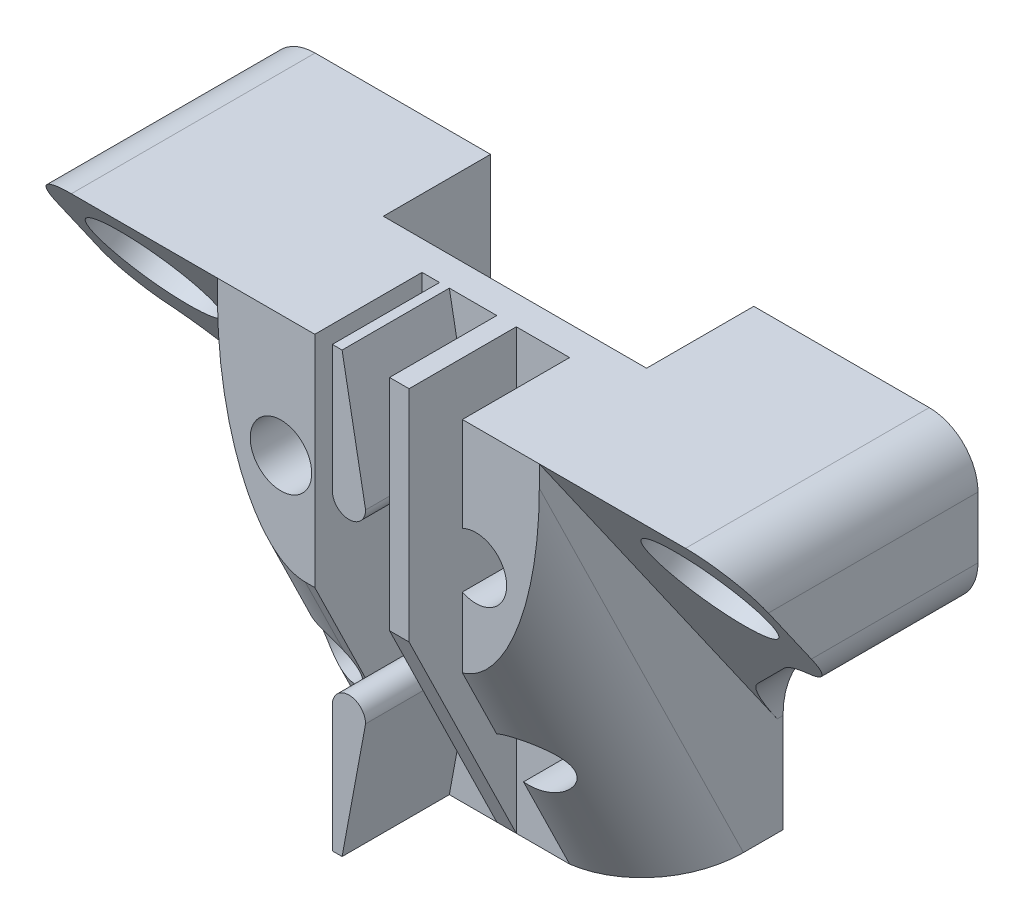
SolidWorks part; units mm, degrees
other "Markup1"
sketch "Sketch5" plane through (36.5, -22.5, 25) normal (0.516, -0.1626, 0.841) x (0.8506, -0.0189, -0.5255)
ref_plane "Front Plane" through (0, 0, 0) normal (0, 0, 1) x (1, 0, 0)
ref_plane "Top Plane" through (0, 0, 0) normal (0, 1, 0) x (1, 0, 0)
ref_plane "Right Plane" through (0, 0, 0) normal (1, 0, 0) x (0, 0, -1)
sketch "Sketch1" plane through (0, 0, 0) normal (0, 0, 1) x (1, 0, 0)
  line L1 (-16.5, -22.5) -> (16.5, -22.5)
  line L2 (-16.5, -22.5) -> (-16.5, 22.5)
  line L3 (-16.5, 22.5) -> (16.5, 22.5)
  line L4 (16.5, -22.5) -> (16.5, 22.5)
  line L5 (-16.5, -22.5) -> (16.5, 22.5) construction
  line L6 (-16.5, 22.5) -> (16.5, -22.5) construction
  point P0 (0, 0)
  dimension "D1" = 33
  dimension "D2" = 45
extrude "Boss-Extrude1" add sketch "Sketch1" along normal blind 14
sketch "Sketch4" plane through (-16.5, 0, 0) normal (-1, 0, 0) x (0, 0, 1)
  line L0 (25, 22.5) -> (14, 6.7904)
  line L1 (0, 22.5) -> (25, 22.5)
  line L2 (0, 22.5) -> (0, 6.7904)
  line L3 (0, 6.7904) -> (14, 6.7904)
  line L5 (14, 22.5) -> (14, -22.5) construction
  point P1 (14, 2.385)
  dimension "D1" = 25
  dimension "D2" = 55
extrude "Boss-Extrude2" add sketch "Sketch4" along normal blind 20 and the other way blind 53
sketch "Sketch6" plane through (0, -4.3439, 6.2037) normal (0, -0.5736, 0.8192) x (1, 0, 0)
  line L0 (-36.5, 23.1814) -> (36.5, 23.1814) construction
  line L1 (-36.5, 13.5924) -> (-36.5, 32.7703) construction
  line L2 (36.5, 13.5924) -> (36.5, 32.7703) construction
  circle A0 centre (-28.5, 23.1814) radius 6.15
  circle A1 centre (28.5, 23.1814) radius 6.15
  dimension "D1" = 12.3
  dimension "D2" = 8
  dimension "D3" = 8
extrude "Cut-Extrude3" cut sketch "Sketch6" against normal blind 4
sketch "Sketch2" plane through (0, 0, 0) normal (0, 0, 1) x (1, 0, 0)
  line L0 (36.5, 22.5) -> (-36.5, 22.5) construction
  line L1 (13.5, -22.5) -> (-13.5, -22.5)
  line L2 (13.5, -22.5) -> (13.5, 22.5)
  line L3 (13.5, 22.5) -> (-13.5, 22.5)
  line L4 (-13.5, -22.5) -> (-13.5, 22.5)
  line L5 (13.5, -22.5) -> (-13.5, 22.5) construction
  line L6 (13.5, 22.5) -> (-13.5, -22.5) construction
  line L7 (16.5, -22.5) -> (16.5, 6.7904) construction
  point P0 (0, 0)
  dimension "D1" = 3
extrude "Cut-Extrude1" cut sketch "Sketch2" along normal offset from surface (11 mm away) 3 up to face at (0, -7.8548, 14)
sketch "Sketch7" plane through (0, 0, 14) normal (0, 0, 1) x (1, 0, 0)
  line L0 (36.5, 22.5) -> (-36.5, 22.5) construction
  line L1 (-16.5, -22.5) -> (16.5, -22.5)
  line L2 (-16.5, -22.5) -> (-16.5, 22.5)
  line L3 (-16.5, 22.5) -> (16.5, 22.5)
  line L4 (16.5, -22.5) -> (16.5, 22.5)
  line L5 (16.5, -22.5) -> (16.5, 6.7904) construction
extrude "Boss-Extrude3" add sketch "Sketch7" along normal blind 11
chamfer "Chamfer1" distance 15 angle 45 2 edges at (16.5, 6.7904, 7) (-16.5, 6.7904, 7)
fillet "Fillet2" radius 10 4 edges at (-16.5, -8.2096, 1.7484) (16.5, -8.2096, 1.7484) (31.5, 6.7904, 7) (-31.5, 6.7904, 7)
sketch "Sketch3" plane through (0, 0, 11) normal (0, 0, 1) x (1, 0, 0)
  line L1 (-10, -10) -> (10, -10) construction
  line L2 (-10, -10) -> (-10, 10) construction
  line L3 (-10, 10) -> (10, 10) construction
  line L4 (10, -10) -> (10, 10) construction
  line L5 (-10, -10) -> (10, 10) construction
  line L6 (-10, 10) -> (10, -10) construction
  circle A0 centre (-10, 10) radius 1.85
  circle A1 centre (10, 10) radius 1.85
  circle A2 centre (10, -10) radius 1.85
  circle A3 centre (-10, -10) radius 1.85
  point P0 (0, 0)
  dimension "D3" = 3.7
  dimension "D1" = 20
  dimension "D2" = 20
extrude "Cut-Extrude2" cut sketch "Sketch3" against normal through all both and the other way through all
sketch "Sketch8" plane through (0, 0, 25) normal (0, 0, 1) x (1, 0, 0)
  line L0 (16.5, 22.5) -> (-16.5, 22.5) construction
  line L1 (-6.53, 22.5) -> (-4.73, 22.5)
  line L2 (-6.53, 22.5) -> (-6.53, -22.5)
  line L3 (-6.53, -22.5) -> (-4.73, -22.5)
  line L4 (-4.73, 22.5) -> (-4.73, -22.5)
  line L5 (-16.5, -22.5) -> (16.5, -22.5) construction
  line L7 (3.14, 22.5) -> (8.61, 22.5)
  line L8 (3.14, 22.5) -> (3.14, -22.5)
  line L9 (3.14, -22.5) -> (8.61, -22.5)
  line L10 (8.61, 22.5) -> (8.61, -22.5)
  dimension "D1" = 4.73
  dimension "D2" = 3.14
  dimension "D3" = 1.8
  dimension "D4" = 5.47
extrude "Cut-Extrude4" cut sketch "Sketch8" against normal offset from surface (11 mm away) 3 up to face at (-11.85, -10, 11)
sketch "Sketch9" plane through (0, 0, 25) normal (0, 0, 1) x (1, 0, 0)
  line L4 (3.14, 22.5) -> (3.14, -22.5) construction
  line L5 (-4.73, -22.5) -> (1.14, -22.5)
  line L6 (-4.73, -22.5) -> (-4.73, 22.5)
  line L8 (1.14, -22.5) -> (1.14, 22.5)
  line L9 (-4.73, -22.5) -> (-4.73, 22.5) construction
  line L10 (-4.73, 22.5) -> (1.14, 22.5)
  point P1 (-4.73, -2.5)
  point P7 (-4.73, -2.5)
  point P11 (1.14, 21.906)
  point P15 (-4.73, 21.9815)
  dimension "D1" = 2
extrude "Cut-Extrude5" cut sketch "Sketch9" against normal up to surface (11 mm away) up to face at (-5.63, 0, 14)
ref_plane "Plane1" through (0, 0, 14) normal (0, 0, 1) x (1, 0, 0)
sketch "Sketch12" plane through (3.14, 0, 0) normal (1, 0, 0) x (0, 0, -1)
  line L0 (-14, -22.5) -> (-25, 0)
  line L1 (-14, 28.8039) -> (-14, -28.8039) construction
  line L2 (-25, -22.5) -> (-25, 22.5) construction
  line L5 (-25, -22.5) -> (0, -22.5) construction
  line L6 (-14, -22.5) -> (-25, -22.5)
  line L7 (-25, -22.5) -> (-25, 0)
  point P6 (-25, 0)
extrude "Cut-Extrude7" cut sketch "Sketch12" along normal blind 25 and the other way blind 25
fillet "Fillet3" radius 9 2 edges at (16.5, -11.25, 19.5) (-16.5, -11.25, 19.5)
sketch "Sketch10" plane through (0, 0, 14) normal (0, 0, 1) x (1, 0, 0)
  line L0 (-4.73, -22.5) -> (-4.73, -9.5)
  line L1 (-6.53, -22.5) -> (1.14, -22.5) construction
  line L2 (-1.3211, -9.5) -> (-3.73, -22.5)
  line L3 (-3.73, -22.5) -> (-4.73, -22.5)
  arc A0 (-4.73, -9.5) -> (-1.3211, -9.5) centre (-3.0255, -9.5) cw
  point P6 (0, 0)
  dimension "D1" = 1
  dimension "D2" = 13
  dimension "D3" = 4.73
extrude "Boss-Extrude4" add sketch "Sketch10" along normal up to surface (11 mm away) up to face at (-8.15, 10, 25)
mirror "Mirror1" about plane through (0, 0, 0) normal (0, 1, 0) of "Boss-Extrude4"
sketch "Sketch13" plane through (0, 0, 14) normal (0, 0, 1) x (1, 0, 0)
  circle A0 centre (10, 10) radius 3.15
  circle A1 centre (10, -10) radius 3.15
  circle A2 centre (-10, -10) radius 3.15
  circle A3 centre (-10, 10) radius 3.15
  dimension "D1" = 6.3
extrude "Cut-Extrude8" cut sketch "Sketch13" along normal through all
fillet "Fillet4" radius 5 4 edges at (36.5, 22.5, 12.5) (-36.5, 22.5, 12.5) (-36.5, 6.7904, 7) (36.5, 6.7904, 7)
